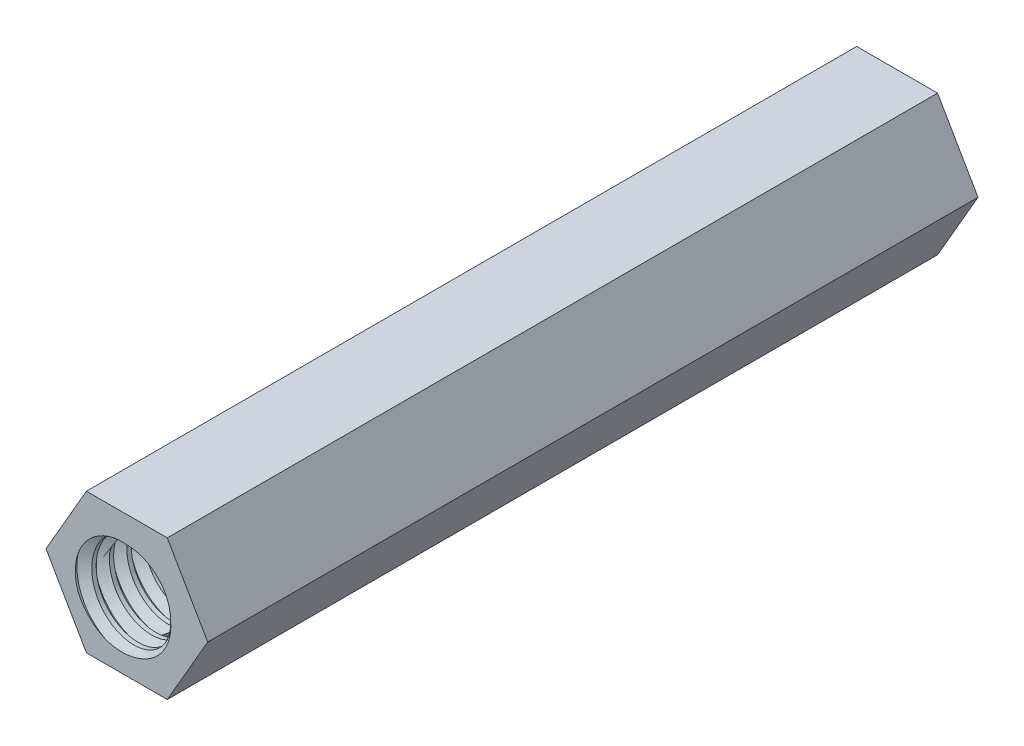
SolidWorks part; units mm, degrees
ref_plane "Front Plane" through (0, 0, 0) normal (0, 0, 1) x (1, 0, 0)
ref_plane "Top Plane" through (0, 0, 0) normal (0, 1, 0) x (1, 0, 0)
ref_plane "Right Plane" through (0, 0, 0) normal (1, 0, 0) x (0, 0, -1)
sketch "Sketch1" plane through (0, 0, 0) normal (0, 0, 1) x (1, 0, 0)
  line L1 (2.3094, 0) -> (1.1547, 2)
  line L2 (1.1547, 2) -> (-1.1547, 2)
  line L3 (-1.1547, 2) -> (-2.3094, 0)
  line L4 (-2.3094, 0) -> (-1.1547, -2)
  line L5 (-1.1547, -2) -> (1.1547, -2)
  line L6 (1.1547, -2) -> (2.3094, 0)
  circle A0 centre (0, 0) radius 2 construction
  dimension "D1" = 4
extrude "Boss-Extrude1" add sketch "Sketch1" against normal blind 22
sketch "Sketch2" plane through (0, 0, 0) normal (0, 0, 1) x (1, 0, 0)
  circle A0 centre (0, 0) radius 1.25
  dimension "D1" = 2.5
extrude "Cut-Extrude1" cut sketch "Sketch2" along normal through all and the other way through all
thread "Thread_M3x0.5_Internal_Through_RH" pitch 0.5 profile "Thread Profile1" start angle 0, offset 0, length 0, pitch 0.5, diameter 2.5
ref_plane "Plane1" through (1.25, 0, -22) normal (0, -1, 0) x (1, 0, 0)
sketch "Thread Profile1" plane through (1.25, 0, -22) normal (0, -1, 0) x (1, 0, 0)
  line L0 (0, 0) -> (0, 0.5) construction
  line L1 (0, 0) -> (0.2706, 0.1562)
  line L2 (0.2706, 0.1562) -> (0.2706, 0.2187)
  line L3 (0.2706, 0.2187) -> (0, 0.375)
  line L4 (0.2706, 0.1875) -> (0, 0.1875) construction
  line L11 (0, 0) -> (0, 0.375)
  point P2 (0, 0)
  dimension "Pitch" = 0.5
  dimension "Profile_Angle" = 60
  dimension "Profile_Land" = 0.0625
  dimension "Profile_Height" = 0.2706
